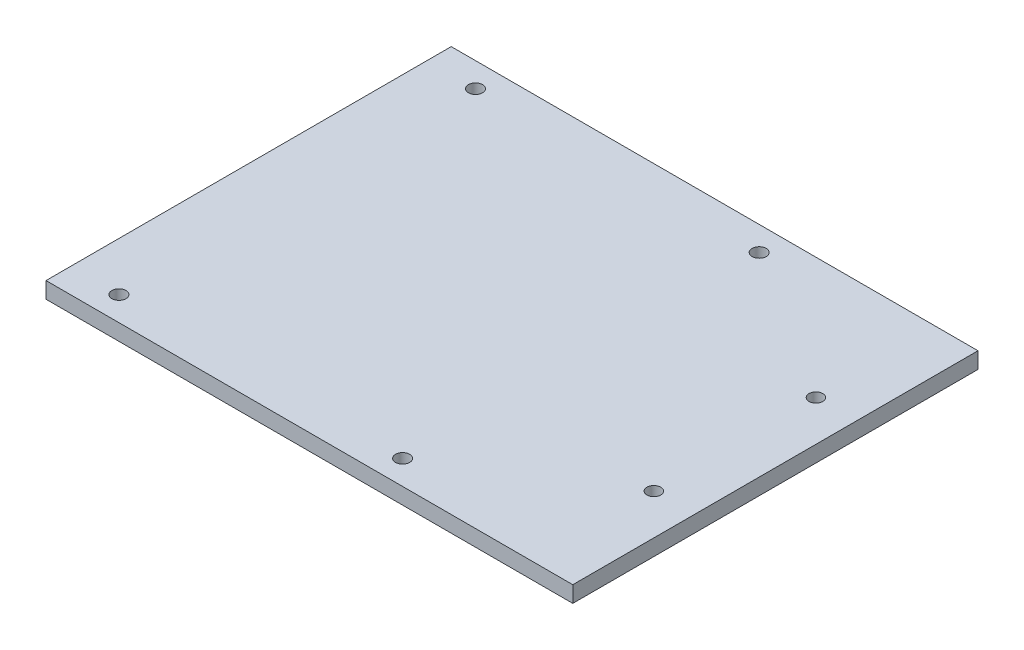
SolidWorks part; units mm, degrees
ref_plane "Front Plane" through (0, 0, 0) normal (0, 0, 1) x (1, 0, 0)
ref_plane "Top Plane" through (0, 0, 0) normal (0, 1, 0) x (1, 0, 0)
ref_plane "Right Plane" through (0, 0, 0) normal (1, 0, 0) x (0, 0, -1)
sketch "Sketch1" plane through (0, 0, 0) normal (0, 1, 0) x (1, 0, 0)
  line L1 (0, 0) -> (130, 0)
  line L2 (0, 0) -> (0, 100)
  line L3 (0, 100) -> (130, 100)
  line L4 (130, 0) -> (130, 100)
  dimension "D1" = 130
  dimension "D2" = 100
extrude "Boss-Extrude1" add sketch "Sketch1" along normal blind 4
sketch "Sketch2" plane through (0, 4, 0) normal (0, 1, 0) x (1, 0, 0)
  line L1 (8.5847, 94.0928) -> (91.5847, 94.0928)
  line L2 (8.5847, 94.0928) -> (8.5847, 36.0928)
  line L3 (8.5847, 36.0928) -> (91.5847, 36.0928)
  line L4 (91.5847, 94.0928) -> (91.5847, 36.0928)
  line L5 (11.157, 30.1999) -> (62.157, 30.1999)
  line L6 (11.157, 30.1999) -> (11.157, 4.1999)
  line L7 (11.157, 4.1999) -> (62.157, 4.1999)
  line L8 (62.157, 30.1999) -> (62.157, 4.1999)
  point P8 (77.2964, 143.745)
  point P9 (76.0498, 140.859)
  point P10 (66.4479, 46.8154)
  point P11 (68.0774, 122.8214)
  point P12 (87.2552, 120.5374)
  point P13 (86.0198, 112.3983)
  point P14 (0, 0)
  point P15 (60.5746, 49.9419)
  point P16 (62.157, 4.1999)
  point P17 (91.5847, 36.0928)
  dimension "D1" = 83
  dimension "D2" = 58
  dimension "D3" = 51
  dimension "D4" = 26
sketch "Sketch4" plane through (0, 4, 0) normal (0, 1, 0) x (1, 0, 0)
  line L0 (130, 50) -> (0, 50) construction
  line L1 (130, 0) -> (130, 100) construction
  line L2 (0, 100) -> (0, 0) construction
  line L3 (65, 100) -> (65, 0) construction
  line L4 (130, 100) -> (0, 100) construction
  line L5 (0, 0) -> (130, 0) construction
  circle A0 centre (120, 30) radius 1.7
  circle A1 centre (120, 70) radius 1.7
  point P16 (117.5583, 70)
  point P17 (0, 0)
  point P18 (0, 0)
  point P19 (119.4478, 70)
  dimension "D3" = 3.4
  dimension "D1" = 20
  dimension "D2" = 20
  dimension "D4" = 10
extrude "Cut-Extrude1" cut sketch "Sketch4" against normal through all
sketch "Sketch6" plane through (0, 0, 0) normal (0, -1, 0) x (1, 0, 0)
  line L0 (0, -50) -> (50, -50) construction
  line L7 (0, -50) -> (130, -50) construction
  line L8 (0, -100) -> (0, 0) construction
  line L9 (130, 0) -> (130, -100) construction
  line L14 (0, -54) -> (50, -54) construction
  line L15 (0, -54) -> (0, -46) construction
  line L16 (0, -46) -> (50, -46) construction
  line L17 (50, -54) -> (50, -46) construction
  line L18 (25, -46) -> (25, -54) construction
  line L20 (50, -50) -> (37.5, -28.3494)
  line L21 (37.5, -28.3494) -> (12.5, -28.3494)
  line L22 (12.5, -28.3494) -> (0, -50)
  line L23 (0, -50) -> (12.5, -71.6506)
  line L24 (12.5, -71.6506) -> (37.5, -71.6506)
  line L25 (37.5, -71.6506) -> (50, -50)
  circle A1 centre (25, -50) radius 21.6506 construction
  point P15 (0, 0)
  dimension "D1" = 50
  dimension "D2" = 8
extrude "Boss-Extrude2" add sketch "Sketch6" along normal blind 16
sketch "Sketch7" plane through (0, 4, 0) normal (0, 1, 0) x (1, 0, 0)
  line L0 (0, 6) -> (130, 6) construction
  line L1 (0, 100) -> (0, 0) construction
  line L2 (130, 0) -> (130, 100) construction
  line L3 (0, 0) -> (130, 0) construction
  line L4 (0, 50) -> (130, 50) construction
  circle A0 centre (12, 6) radius 1.75
  circle A1 centre (82, 6) radius 1.75
  circle A2 centre (82, 94) radius 1.75
  circle A3 centre (12, 94) radius 1.75
  dimension "D1" = 3.5
  dimension "D2" = 3.5
  dimension "D3" = 70
  dimension "D4" = 12
  dimension "D5" = 6
extrude "Cut-Extrude2" cut sketch "Sketch7" against normal through all
